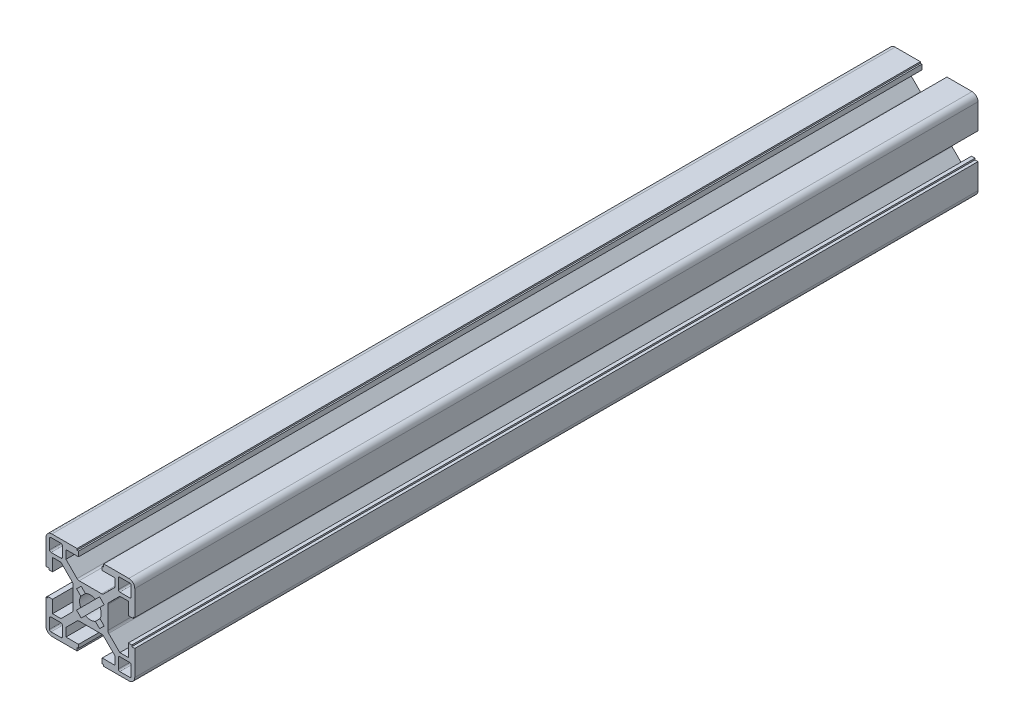
SolidWorks part; units mm, degrees
material "6061-T6 (SS)"
ref_plane "Front Plane" through (0, 0, 0) normal (0, 0, 1) x (1, 0, 0)
ref_plane "Top Plane" through (0, 0, 0) normal (0, 1, 0) x (1, 0, 0)
ref_plane "Right Plane" through (0, 0, 0) normal (1, 0, 0) x (0, 0, -1)
sketch "Sketch1" plane through (0, 0, 0) normal (0, 0, 1) x (1, 0, 0)
  line L0 (-4.5, 15) -> (-4.5, 14.5)
  line L1 (13, -15) -> (4.5, -15)
  line L2 (15, -13) -> (15, -4.5)
  line L3 (13, 15) -> (4.5, 15)
  line L4 (-15, -13) -> (-15, -4.5)
  line L5 (15, -15) -> (-15, 15) construction
  line L6 (15, 15) -> (-15, -15) construction
  line L7 (-4.5, 14.5) -> (-4, 14.5)
  line L8 (-4, 14.5) -> (-4, 12.8)
  line L9 (-4, 12.8) -> (-8.25, 12.8)
  line L10 (-8.25, 12.8) -> (-8.25, 9.95)
  line L11 (-8.25, 9.95) -> (-4.4929, 6.1929)
  line L12 (-3.7858, 5.9) -> (3.7858, 5.9)
  line L13 (4.4929, 6.1929) -> (8.25, 9.95)
  line L14 (8.25, 9.95) -> (8.25, 12.8)
  line L15 (8.25, 12.8) -> (4, 12.8)
  line L16 (4, 12.8) -> (4, 14)
  line L17 (4, 14) -> (4.5, 14)
  line L18 (4.5, 14) -> (4.5, 15)
  line L19 (0, 0) -> (0, 16.8698) construction
  line L20 (-4.5, 15) -> (-13, 15)
  line L21 (12.8, 8.25) -> (9.95, 8.25)
  line L22 (9.95, 8.25) -> (6.1929, 4.4929)
  line L23 (5.9, 3.7858) -> (5.9, -3.7858)
  line L24 (6.1929, -4.4929) -> (9.95, -8.25)
  line L25 (9.95, -8.25) -> (12.8, -8.25)
  line L26 (12.8, -8.25) -> (12.8, -4)
  line L27 (12.8, 4) -> (12.8, 8.25)
  line L28 (12.8, -4) -> (14, -4)
  line L29 (14, -4) -> (14, -4.5)
  line L30 (14, -4.5) -> (15, -4.5)
  line L31 (14.5, 4) -> (12.8, 4)
  line L32 (14.5, 4.5) -> (14.5, 4)
  line L33 (15, 4.5) -> (14.5, 4.5)
  line L34 (8.25, -12.8) -> (8.25, -9.95)
  line L35 (8.25, -9.95) -> (4.4929, -6.1929)
  line L36 (3.7858, -5.9) -> (-3.7858, -5.9)
  line L37 (-4.4929, -6.1929) -> (-8.25, -9.95)
  line L38 (-8.25, -9.95) -> (-8.25, -12.8)
  line L39 (-8.25, -12.8) -> (-4, -12.8)
  line L40 (4, -12.8) -> (8.25, -12.8)
  line L41 (-4, -12.8) -> (-4, -14)
  line L42 (-4, -14) -> (-4.5, -14)
  line L43 (-4.5, -14) -> (-4.5, -15)
  line L44 (4, -14.5) -> (4, -12.8)
  line L45 (4.5, -14.5) -> (4, -14.5)
  line L46 (4.5, -15) -> (4.5, -14.5)
  line L47 (-12.8, -8.25) -> (-9.95, -8.25)
  line L48 (-9.95, -8.25) -> (-6.1929, -4.4929)
  line L49 (-5.9, -3.7858) -> (-5.9, 3.7858)
  line L50 (-6.1929, 4.4929) -> (-9.95, 8.25)
  line L51 (-9.95, 8.25) -> (-12.8, 8.25)
  line L52 (-12.8, 8.25) -> (-12.8, 4)
  line L53 (-12.8, -4) -> (-12.8, -8.25)
  line L54 (-12.8, 4) -> (-14, 4)
  line L55 (-14, 4) -> (-14, 4.5)
  line L56 (-14, 4.5) -> (-15, 4.5)
  line L57 (-14.5, -4) -> (-12.8, -4)
  line L58 (-14.5, -4.5) -> (-14.5, -4)
  line L59 (-15, -4.5) -> (-14.5, -4.5)
  line L60 (15, 4.5) -> (15, 13)
  line L61 (-15, 4.5) -> (-15, 13)
  line L62 (-4.5, -15) -> (-13, -15)
  line L63 (13.3, -9.45) -> (9.95, -9.45)
  line L64 (9.95, 13.8) -> (13.3, 13.8)
  line L65 (9.45, 13.3) -> (9.45, 9.95)
  line L66 (9.95, 9.45) -> (13.3, 9.45)
  line L67 (13.8, 13.3) -> (13.8, 9.95)
  line L68 (13.8, -9.95) -> (13.8, -13.3)
  line L69 (13.3, -13.8) -> (9.95, -13.8)
  line L70 (9.45, -9.95) -> (9.45, -13.3)
  line L71 (-9.45, -13.3) -> (-9.45, -9.95)
  line L72 (-9.95, -13.8) -> (-13.3, -13.8)
  line L73 (-13.8, -13.3) -> (-13.8, -9.95)
  line L74 (-9.95, -9.45) -> (-13.3, -9.45)
  line L75 (-13.3, 9.45) -> (-9.95, 9.45)
  line L76 (-13.8, 9.95) -> (-13.8, 13.3)
  line L77 (-13.3, 13.8) -> (-9.95, 13.8)
  line L78 (-9.45, 9.95) -> (-9.45, 13.3)
  line L79 (-1.6831, -3.2388) -> (-3.1113, -4.6669)
  line L80 (3.1113, 4.6669) -> (4.6669, 3.1113)
  line L81 (4.6669, 3.1113) -> (3.2388, 1.6831)
  line L82 (-3.1113, -4.6669) -> (-4.6669, -3.1113)
  line L83 (-4.6669, -3.1113) -> (-3.2388, -1.6831)
  line L85 (3.1113, -4.6669) -> (4.6669, -3.1113)
  line L86 (3.1113, -4.6669) -> (1.6831, -3.2388)
  line L87 (-4.6669, 3.1113) -> (-3.1113, 4.6669)
  line L88 (-3.1113, 4.6669) -> (-1.6831, 3.2388)
  line L93 (3.2388, -1.6831) -> (4.6669, -3.1113)
  line L95 (1.6831, 3.2388) -> (3.1113, 4.6669)
  line L98 (-3.2388, 1.6831) -> (-4.6669, 3.1113)
  arc A0 (-3.2388, 1.6831) -> (-3.2388, -1.6831) centre (0, 0) ccw
  arc A1 (13, 15) -> (15, 13) centre (13, 13) cw
  arc A2 (15, -13) -> (13, -15) centre (13, -13) cw
  arc A3 (-13, -15) -> (-15, -13) centre (-13, -13) cw
  arc A4 (-15, 13) -> (-13, 15) centre (-13, 13) cw
  arc A5 (-6.1929, 4.4929) -> (-5.9, 3.7858) centre (-6.9, 3.7858) cw
  arc A6 (9.95, 13.8) -> (9.45, 13.3) centre (9.95, 13.3) ccw
  arc A7 (-5.9, -3.7858) -> (-6.1929, -4.4929) centre (-6.9, -3.7858) cw
  arc A8 (-4.4929, -6.1929) -> (-3.7858, -5.9) centre (-3.7858, -6.9) cw
  arc A9 (9.45, 9.95) -> (9.95, 9.45) centre (9.95, 9.95) ccw
  arc A10 (13.8, 9.95) -> (13.3, 9.45) centre (13.3, 9.95) cw
  arc A11 (13.8, 13.3) -> (13.3, 13.8) centre (13.3, 13.3) ccw
  arc A12 (13.8, -9.95) -> (13.3, -9.45) centre (13.3, -9.95) ccw
  arc A13 (13.3, -13.8) -> (13.8, -13.3) centre (13.3, -13.3) ccw
  arc A14 (9.95, -13.8) -> (9.45, -13.3) centre (9.95, -13.3) cw
  arc A15 (9.95, -9.45) -> (9.45, -9.95) centre (9.95, -9.95) ccw
  arc A16 (1.6831, 3.2388) -> (-1.6831, 3.2388) centre (0, 0) ccw
  arc A17 (-9.95, -13.8) -> (-9.45, -13.3) centre (-9.95, -13.3) ccw
  arc A18 (-13.8, -13.3) -> (-13.3, -13.8) centre (-13.3, -13.3) ccw
  arc A19 (-13.8, -9.95) -> (-13.3, -9.45) centre (-13.3, -9.95) cw
  arc A20 (-9.45, -9.95) -> (-9.95, -9.45) centre (-9.95, -9.95) ccw
  arc A21 (1.6831, 3.2388) -> (-1.6831, 3.2388) centre (0, 0) ccw
  arc A22 (-13.8, 9.95) -> (-13.3, 9.45) centre (-13.3, 9.95) ccw
  arc A23 (-13.3, 13.8) -> (-13.8, 13.3) centre (-13.3, 13.3) ccw
  arc A24 (-9.95, 13.8) -> (-9.45, 13.3) centre (-9.95, 13.3) cw
  arc A25 (-9.95, 9.45) -> (-9.45, 9.95) centre (-9.95, 9.95) ccw
  arc A26 (3.2388, -1.6831) -> (3.2388, 1.6831) centre (0, 0) ccw
  arc A27 (3.7858, -5.9) -> (4.4929, -6.1929) centre (3.7858, -6.9) cw
  arc A28 (6.1929, -4.4929) -> (5.9, -3.7858) centre (6.9, -3.7858) cw
  arc A29 (5.9, 3.7858) -> (6.1929, 4.4929) centre (6.9, 3.7858) cw
  arc A30 (4.4929, 6.1929) -> (3.7858, 5.9) centre (3.7858, 6.9) cw
  arc A31 (-3.7858, 5.9) -> (-4.4929, 6.1929) centre (-3.7858, 6.9) cw
  arc A32 (3.2388, -1.6831) -> (3.2388, 1.6831) centre (0, 0) ccw
  arc A33 (-3.2388, 1.6831) -> (-3.2388, -1.6831) centre (0, 0) ccw
  arc A34 (-1.6831, -3.2388) -> (1.6831, -3.2388) centre (0, 0) ccw
  arc A35 (-1.6831, -3.2388) -> (1.6831, -3.2388) centre (0, 0) ccw
  point P0 (0, 0)
  point P70 (0, 0)
  point P135 (0, 0)
  point P144 (4.2, 5.9)
  point P147 (-4.2, 5.9)
  point P151 (0, 0)
  point P154 (3.8891, 3.8891)
  point P159 (0, 0)
  point P162 (3.8891, -3.8891)
  dimension "D18" = 7.3
  dimension "D20" = 2
  dimension "D21" = 1
  dimension "D22" = 1.2
  dimension "D23" = 30
  dimension "D28" = 0.5
  dimension "D1" = 30
  dimension "D2" = 30
  dimension "D3" = 8
  dimension "D4" = 4
  dimension "D5" = 9
  dimension "D6" = 4.5
  dimension "D7" = 1
  dimension "D8" = 0.5
  dimension "D9" = 16.5
  dimension "D10" = 8.25
  dimension "D11" = 2.2
  dimension "D12" = 2.2
  dimension "D13" = 9.1
  dimension "D14" = 2.4042
  dimension "D16" = 45
  dimension "D17" = 45
  dimension "D25" = 1.2
  dimension "D26" = 1.2
  dimension "D27" = 1.2
  dimension "D19" = 4
extrude "Boss-Extrude1" add sketch "Sketch1" along normal blind 285 contours A0 | L75 A25 L78 A24 L77 A23 L76 A22 | L71 A20 L74 A19 L73 A18 L72 A17 | L63 A15 L70 A14 L69 A13 L68 A12 | L67 A11 L64 A6 L65 A9 L66 A10 | L36 A8 L37 L38 L39 L41 L42 L43 L62 A3 L4 L59 L58 L57 L53 L47 L48 A7 L49 A5 L50 L51 L52 L54 L55 L56 L61 A4 L20 L0 L7 L8 L9 L10 L11 A31 L12 A30 L13 L14 L15 L16 L17 L18 L3 A1 L60 L33 L32 L31 L27 L21 L22 A29 L23 A28 L24 L25 L26 L28 L29 L30 L2 A2 L1 L46 L45 L44 L40 L34 L35 A27 region at (11.625, -11.625, 0) region at (11.625, 11.625, 0) region at (-11.625, -11.625, 0) region at (-11.625, 11.625, 0) region at (0, 0, 0)
